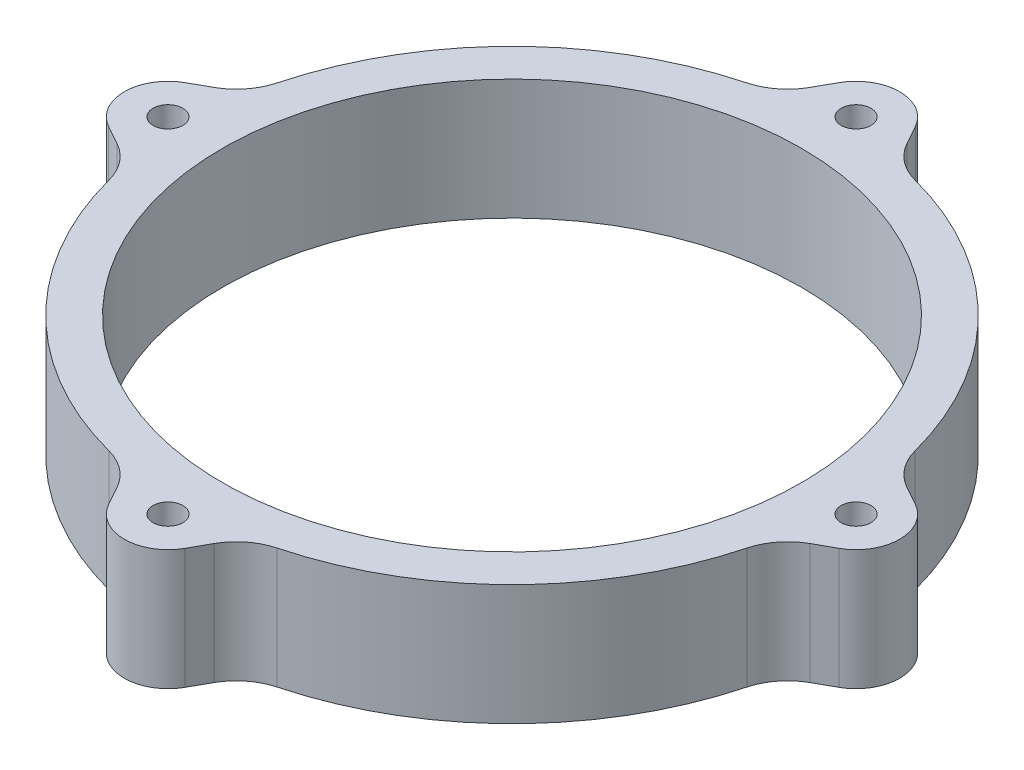
SolidWorks part; units mm, degrees
ref_plane "正面" through (0, 0, 0) normal (0, 0, 1) x (1, 0, 0)
ref_plane "平面" through (0, 0, 0) normal (0, 1, 0) x (1, 0, 0)
ref_plane "右側面" through (0, 0, 0) normal (1, 0, 0) x (0, 0, -1)
sketch "ｽｹｯﾁ1" plane through (0, 0, 0) normal (0, 1, 0) x (1, 0, 0)
  line L0 (0, 0) -> (0, 60) construction
  line L1 (-6.6411, 63.6954) -> (-10.6411, 56.5068)
  line L2 (6.6411, 63.6954) -> (10.6411, 56.5068)
  line L3 (63.6954, 6.6411) -> (56.5068, 10.6411)
  line L4 (63.6954, -6.6411) -> (56.5068, -10.6411)
  line L5 (6.6411, -63.6954) -> (10.6411, -56.5068)
  line L6 (-6.6411, -63.6954) -> (-10.6411, -56.5068)
  line L7 (-63.6954, -6.6411) -> (-56.5068, -10.6411)
  line L8 (-63.6954, 6.6411) -> (-56.5068, 10.6411)
  line L9 (-60, 0) -> (0, 0) construction
  line L10 (0, 0) -> (0, -60) construction
  arc A0 (-10.6411, 56.5068) -> (-56.5068, 10.6411) centre (0, 0) ccw
  circle A1 centre (0, 0) radius 50.5
  circle A2 centre (0, 60) radius 2.6
  arc A3 (6.6411, 63.6954) -> (-6.6411, 63.6954) centre (0, 60) ccw
  circle A4 centre (0, 60) radius 7.6 construction
  circle A5 centre (60, 0) radius 2.6
  arc A6 (63.6954, -6.6411) -> (63.6954, 6.6411) centre (60, 0) ccw
  circle A7 centre (0, -60) radius 2.6
  arc A8 (-6.6411, -63.6954) -> (6.6411, -63.6954) centre (0, -60) ccw
  circle A9 centre (-60, 0) radius 2.6
  arc A10 (-63.6954, 6.6411) -> (-63.6954, -6.6411) centre (-60, 0) ccw
  arc A11 (-56.5068, -10.6411) -> (-10.6411, -56.5068) centre (0, 0) ccw
  arc A12 (10.6411, -56.5068) -> (56.5068, -10.6411) centre (0, 0) ccw
  arc A13 (56.5068, 10.6411) -> (10.6411, 56.5068) centre (0, 0) ccw
  dimension "D1" = 101
  dimension "D2" = 115
  dimension "D3" = 60
  dimension "D4" = 5.2
  dimension "D6" = 4
  dimension "D5" = 5
  dimension "D7" = 4
extrude "ﾎﾞｽ - 押し出し1" add sketch "ｽｹｯﾁ1" along normal blind 21
fillet "ﾌｨﾚｯﾄ1" radius 10 8 edges at (56.5068, 10.5, 10.6411) (56.5068, 10.5, -10.6411) (10.6411, 10.5, -56.5068) (-10.6411, 10.5, -56.5068) (-56.5068, 10.5, -10.6411) (-56.5068, 10.5, 10.6411) (-10.6411, 10.5, 56.5068) (10.6411, 10.5, 56.5068)
